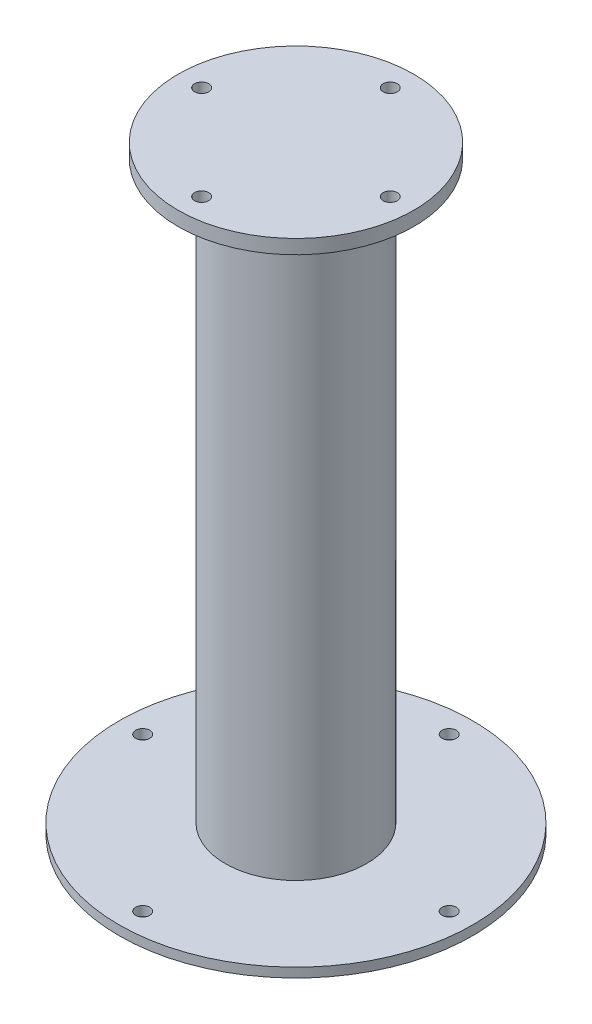
SolidWorks part; units mm, degrees
ref_plane "Front Plane" through (0, 0, 0) normal (0, 0, 1) x (1, 0, 0)
ref_plane "Top Plane" through (0, 0, 0) normal (0, 1, 0) x (1, 0, 0)
ref_plane "Right Plane" through (0, 0, 0) normal (1, 0, 0) x (0, 0, -1)
sketch "Sketch2" plane through (0, 0, 0) normal (0, 1, 0) x (1, 0, 0)
  circle A0 centre (0, 0) radius 37.5
  dimension "D1" = 75
extrude "Boss-Extrude1" add sketch "Sketch2" along normal blind 2
sketch "Sketch4" plane through (0, 2, 0) normal (0, 1, 0) x (1, 0, 0)
  circle A0 centre (0, 0) radius 15
  dimension "D1" = 30
extrude "Boss-Extrude2" add sketch "Sketch4" along normal blind 61
mirror "Mirror1" about plane through (0, 63, 0) normal (0, 1, 0) of "Boss-Extrude2"
sketch "Sketch5" plane through (0, 124, 0) normal (0, 1, 0) x (1, 0, 0)
  circle A0 centre (0, 0) radius 25
  dimension "D1" = 50
extrude "Boss-Extrude3" add sketch "Sketch5" along normal blind 3
sketch "Sketch6" plane through (0, 127, 0) normal (0, 1, 0) x (1, 0, 0)
  circle A0 centre (0, 0) radius 20 construction
  circle A1 centre (0, 20) radius 1.5
  circle A2 centre (20, 0) radius 1.5
  circle A3 centre (0, -20) radius 1.5
  circle A4 centre (-20, 0) radius 1.5
  dimension "D1" = 40
  dimension "D2" = 3
  dimension "D3" = 4
extrude "Cut-Extrude1" cut sketch "Sketch6" against normal up to next
sketch "Sketch7" plane through (0, 0, 0) normal (0, -1, 0) x (1, 0, 0)
  circle A0 centre (0, 0) radius 32.5 construction
  circle A1 centre (0, 32.5) radius 1.5
  circle A2 centre (32.5, 0) radius 1.5
  circle A3 centre (0, -32.5) radius 1.5
  circle A4 centre (-32.5, 0) radius 1.5
  dimension "D1" = 65
  dimension "D2" = 3
  dimension "D3" = 4
extrude "Cut-Extrude2" cut sketch "Sketch7" against normal up to next
shell "Shell1" thickness 2 removed face at (0, 0, 31)
equation "\"D1@Sketch7\"=32.5*2"
